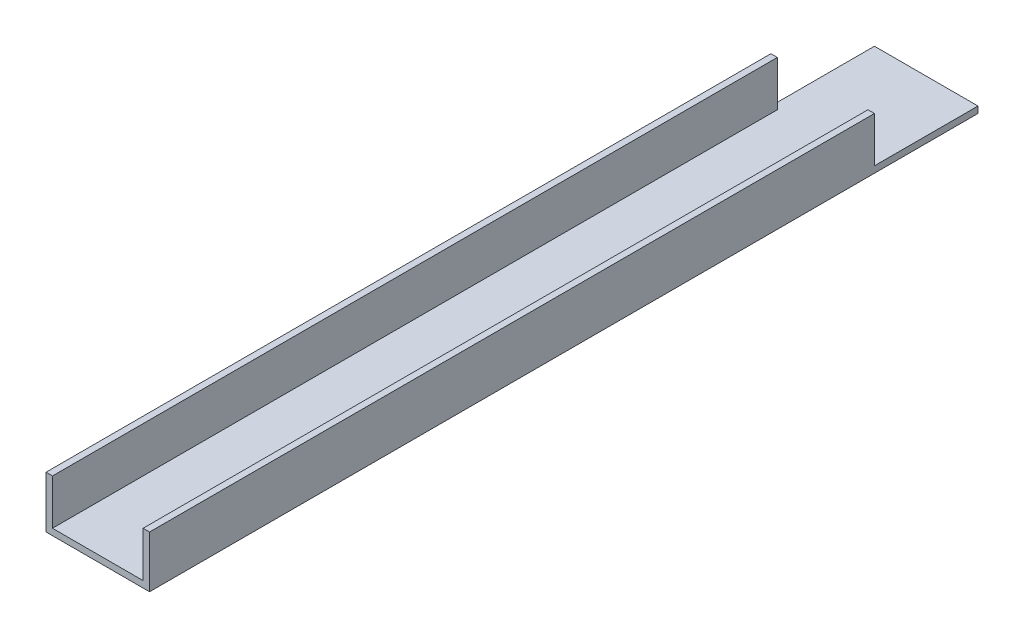
SolidWorks part; units mm, degrees
material "6063-T6"
ref_plane "Front" through (0, 0, 0) normal (0, 0, 1) x (1, 0, 0)
ref_plane "Top" through (0, 0, 0) normal (0, 1, 0) x (1, 0, 0)
ref_plane "Right" through (0, 0, 0) normal (1, 0, 0) x (0, 0, -1)
sketch "Sketch1" plane through (0, 0, 0) normal (0, 0, 1) x (1, 0, 0)
  line L0 (3.175, 3.175) -> (3.175, 25.4)
  line L1 (0, 0) -> (50.8, 0)
  line L2 (0, 0) -> (0, 25.4)
  line L4 (50.8, 0) -> (50.8, 25.4)
  line L5 (3.175, 3.175) -> (47.625, 3.175)
  line L6 (47.625, 3.175) -> (47.625, 25.4)
  line L7 (0, 25.4) -> (3.175, 25.4)
  line L8 (50.8, 25.4) -> (47.625, 25.4)
  dimension "D1" = 25.4
  dimension "D2" = 50.8
  dimension "D3" = 3.175
extrude "Boss-Extrude1" add sketch "Sketch1" along normal blind 406.4
sketch "Sketch2" plane through (0, 25.4, 0) normal (0, 1, 0) x (1, 0, 0)
  line L0 (0, -406.4) -> (0, 0) construction
  line L1 (50.8, 0) -> (0, 0)
  line L2 (50.8, 0) -> (50.8, -50.8)
  line L3 (50.8, -50.8) -> (0, -50.8)
  line L4 (0, 0) -> (0, -50.8)
  line L5 (50.8, 0) -> (0, -50.8) construction
  line L6 (50.8, -50.8) -> (0, 0) construction
  point P4 (25.4, -25.4)
  dimension "D1" = 50.8
extrude "Cut-Extrude1" cut sketch "Sketch2" against normal up to surface (22.225 mm away) up to face at (25.4, 3.175, 203.2)
